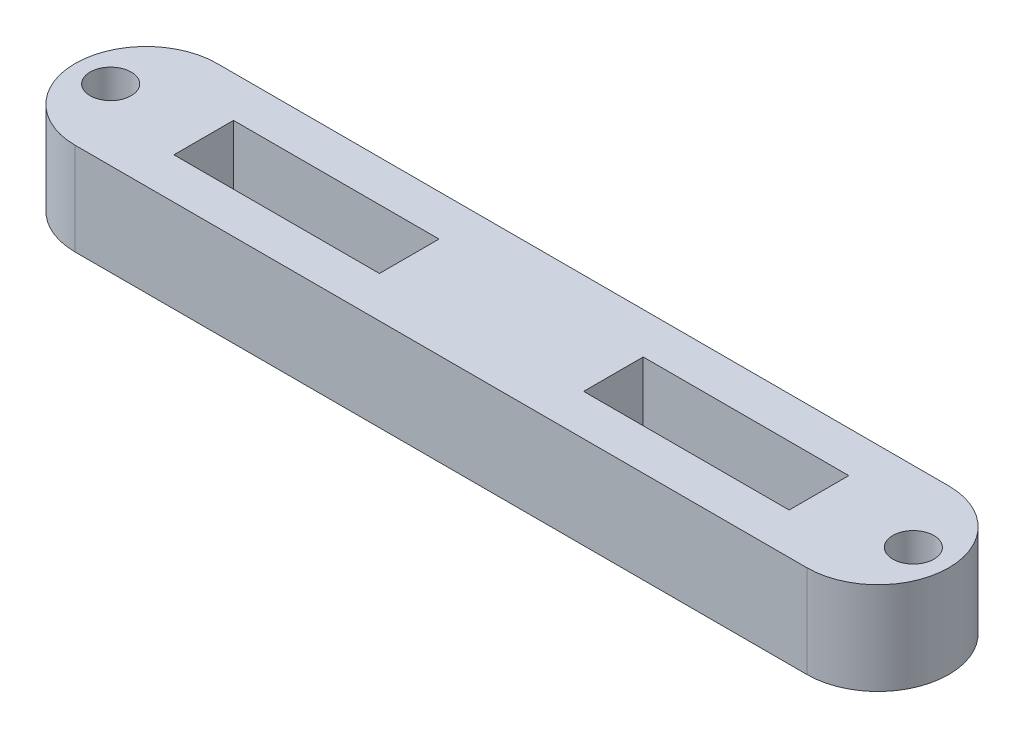
SolidWorks part; units mm, degrees
ref_plane "Front Plane" through (0, 0, 0) normal (0, 0, 1) x (1, 0, 0)
ref_plane "Top Plane" through (0, 0, 0) normal (0, 1, 0) x (1, 0, 0)
ref_plane "Right Plane" through (0, 0, 0) normal (1, 0, 0) x (0, 0, -1)
sketch "Sketch1" plane through (0, 0, 0) normal (0, 1, 0) x (1, 0, 0)
  line L0 (-9.525, 0.9208) -> (-9.525, -0.9207)
  line L2 (10.033, -0.9207) -> (10.033, 0.9208)
  line L4 (-10.033, -0.9208) -> (-10.033, 0.9207)
  line L9 (9.4837, 0.9208) -> (9.4837, -0.9207)
  line L10 (11.3047, 2.1907) -> (-11.3047, 2.1907)
  line L11 (2.6257, 0.9208) -> (2.6257, -0.9207)
  line L12 (11.3047, 2.1907) -> (11.3047, -2.1907)
  line L13 (11.3047, -2.1907) -> (-11.3047, -2.1907)
  line L14 (-11.3047, 2.1907) -> (-11.3047, -2.1907)
  line L15 (11.3047, 2.1907) -> (-11.3047, -2.1907) construction
  line L16 (11.3047, -2.1907) -> (-11.3047, 2.1907) construction
  line L17 (-9.525, 0.9208) -> (-3.175, 0.9208)
  line L18 (-9.525, 0.9208) -> (-9.525, -0.9207)
  line L19 (-9.525, -0.9207) -> (-3.175, -0.9207)
  line L20 (-3.175, 0.9208) -> (-3.175, -0.9207)
  line L21 (9.4837, 0.9208) -> (3.1337, 0.9208)
  line L22 (9.4837, 0.9208) -> (9.4837, -0.9207)
  line L23 (9.4837, -0.9207) -> (3.1337, -0.9207)
  line L24 (3.1337, 0.9208) -> (3.1337, -0.9207)
  line L26 (-3.175, 0.9208) -> (-3.175, -0.9207)
  line L28 (-2.667, 0.9208) -> (-2.667, -0.9207)
  point P0 (0, 0)
  point P6 (0, 0)
  point P7 (0, 0)
  point P8 (0, 0)
  point P14 (0, 0)
  dimension "D1" = 1.8415
  dimension "D2" = 20.066
  dimension "D3" = 6.35
  dimension "D4" = 6.35
  dimension "D5" = 0.508
  dimension "D6" = 0.508
  dimension "D7" = 4.3815
extrude "Boss-Extrude1" add sketch "Sketch1" along normal blind 6.35 contours L10 L14 L13 L12 L24 L21 L9 L23 L17 L20 L19 L0 region at (0.0064, 0, 0)
ref_plane "Plane1" through (0, 0, 0) normal (0, 0, 1) x (1, 0, 0)
sketch "Sketch2" plane through (0, 0, 0) normal (0, 0, 1) x (1, 0, 0)
  line L0 (3.175, 0) -> (-3.175, 0)
  line L1 (11.3047, 0) -> (-11.3047, 0) construction
  arc A0 (-3.175, 0) -> (3.175, 0) centre (0, 0) ccw
  point P6 (0, 0)
  dimension "D1" = 6.35
extrude "Boss-Extrude2" add sketch "Sketch2" against normal up to surface (2.1907 mm away) up to face at (0, 3.175, -2.1907)
extrude "Boss-Extrude3" add sketch "Sketch2<3>" along normal up to surface (2.1907 mm away) up to face at (0, 3.175, 2.1907)
sketch "Sketch2<3>" plane through (0, 0, 0) normal (0, 0, 1) x (1, 0, 0) same geometry as "Sketch2"
sketch "Sketch6" plane through (0, 0, 0) normal (0, -1, 0) x (1, 0, 0)
  line L0 (-9.525, 0.9207) -> (-11.3047, 0.9207)
  line L1 (-11.3047, -2.1907) -> (-11.3047, 2.1907) construction
  line L2 (9.4837, 0.9207) -> (11.3047, 0.9207)
  line L3 (11.3047, -2.1907) -> (11.3047, 2.1907) construction
sketch "Sketch7" plane through (0, 0, 2.1907) normal (0, 0, 1) x (1, 0, 0)
  line L0 (-11.3047, 0) -> (-11.3047, -12.7)
  line L2 (-9.525, 0) -> (-11.3047, 0)
  line L5 (-11.3047, 0) -> (-11.3047, -12.7)
  line L6 (-9.525, 0) -> (-9.525, -10.9203)
  circle A0 centre (-9.525, -12.7) radius 1.5875
  arc A2 (-11.3047, -12.7) -> (-9.525, -10.9203) centre (-9.525, -12.7) ccw
  point P11 (-7.9375, -12.7)
  point P12 (-7.9375, -12.7)
  point P13 (-9.525, -11.1125)
  point P15 (-11.1125, -12.7)
  line M12 (-11.3047, 0) -> (-3.175, 0)
  dimension "D1" = 12.7
extrude "Boss-Extrude4" add sketch "Sketch7" against normal blind 1.27 contours L0 A2 L6 A0 M12 region at (-10.3483, -6.3045, 2.1907)
mirror "Mirror1" about plane through (0, 0, 0) normal (1, 0, 0) of "Boss-Extrude4"
mirror "Mirror2" about plane through (0, 0, 0) normal (0, 0, 1) of "Mirror1"
sketch "Sketch8" plane through (0, 6.35, 0) normal (0, 1, 0) x (1, 0, 0)
  line L0 (-11.3047, 2.1907) -> (-11.3047, -2.1907)
  line L1 (0, 0) -> (0, 2.1907) construction
  line L3 (11.3047, 2.1907) -> (-11.3047, 2.1907) construction
  line L5 (11.3047, 2.1908) -> (11.3047, -2.1907)
  arc A0 (-11.3047, 2.1907) -> (-11.3047, -2.1907) centre (-11.3047, 0) ccw
  circle A1 centre (12.4001, 0) radius 0.635
  circle A2 centre (-12.4001, 0) radius 0.635
  arc A3 (11.3047, 2.1908) -> (11.3047, -2.1907) centre (11.3047, 0) cw
  dimension "D1" = 1.27
extrude "Boss-Extrude5" add sketch "Sketch8" against normal blind 1.27 and the other way blind 6.35
sketch "Sketch9" plane through (0, 0, -2.1907) normal (0, 0, -1) x (-1, 0, 0)
  line L0 (11.3047, 6.35) -> (11.3047, 12.7)
  line L2 (-11.3047, 6.35) -> (11.3047, 6.35)
  line L3 (-11.3047, 6.35) -> (-11.3047, 12.7)
  line L4 (-11.3047, 12.7) -> (11.3047, 12.7)
  line L5 (11.3047, 6.35) -> (11.3047, 12.7)
  dimension "D1" = 6.35
extrude "Boss-Extrude6" add sketch "Sketch9" against normal up to surface (4.3815 mm away) contours L3 L2 L5 L4 up to face at (0, -2.6543, 2.1907)
sketch "Sketch10" plane through (0, 12.7, 0) normal (0, 1, 0) x (1, 0, 0)
  line L1 (-9.525, 0.9208) -> (-3.175, 0.9208)
  line L2 (-9.525, 0.9208) -> (-9.525, -0.9207)
  line L3 (-9.525, -0.9207) -> (-3.175, -0.9207)
  line L4 (-3.175, 0.9208) -> (-3.175, -0.9207)
  line L5 (3.1337, 0.9208) -> (9.4837, 0.9208)
  line L6 (3.1337, 0.9208) -> (3.1337, -0.9207)
  line L7 (3.1337, -0.9207) -> (9.4837, -0.9207)
  line L8 (9.4837, 0.9208) -> (9.4837, -0.9207)
extrude "Cut-Extrude1" cut sketch "Sketch10" against normal up to surface (12.7 mm away) contours L8 L5 L6 L7 | L2 L1 L4 L3 region at (6.3087, 12.7, 0) up to face at (-6.35, 0, 1.5557)
sketch "Sketch11" plane through (0, 12.7, 0) normal (0, 1, 0) x (1, 0, 0)
  line L0 (-11.3047, 2.1907) -> (-11.3047, -2.1907) construction
  line L1 (-11.3047, 2.1907) -> (-11.3047, -2.1907)
  line L2 (0, 0) -> (0, 2.1907) construction
  line L3 (11.3047, 2.1908) -> (11.3047, -2.1907)
  circle A0 centre (-12.4001, 0) radius 0.635
  arc A1 (-11.3047, 2.1907) -> (-11.3047, -2.1907) centre (-11.3047, 0) ccw
  arc A2 (11.3047, 2.1908) -> (11.3047, -2.1907) centre (11.3047, 0) cw
  circle A3 centre (12.4001, 0) radius 0.635
ref_plane "Plane2" through (0, 5.08, 0) normal (0, -1, 0) x (-1, 0, 0)
sketch "Sketch12" plane through (0, 5.08, 0) normal (0, -1, 0) x (-1, 0, 0)
  line L1 (-15.9012, 8.618) -> (15.7326, 8.618)
  line L2 (-15.9012, 8.618) -> (-15.9012, -5.839)
  line L3 (-15.9012, -5.839) -> (15.7326, -5.839)
  line L4 (15.7326, 8.618) -> (15.7326, -5.839)
extrude "Cut-Extrude2" cut sketch "Sketch12" along normal blind 23.114 and the other way blind 4.7625
